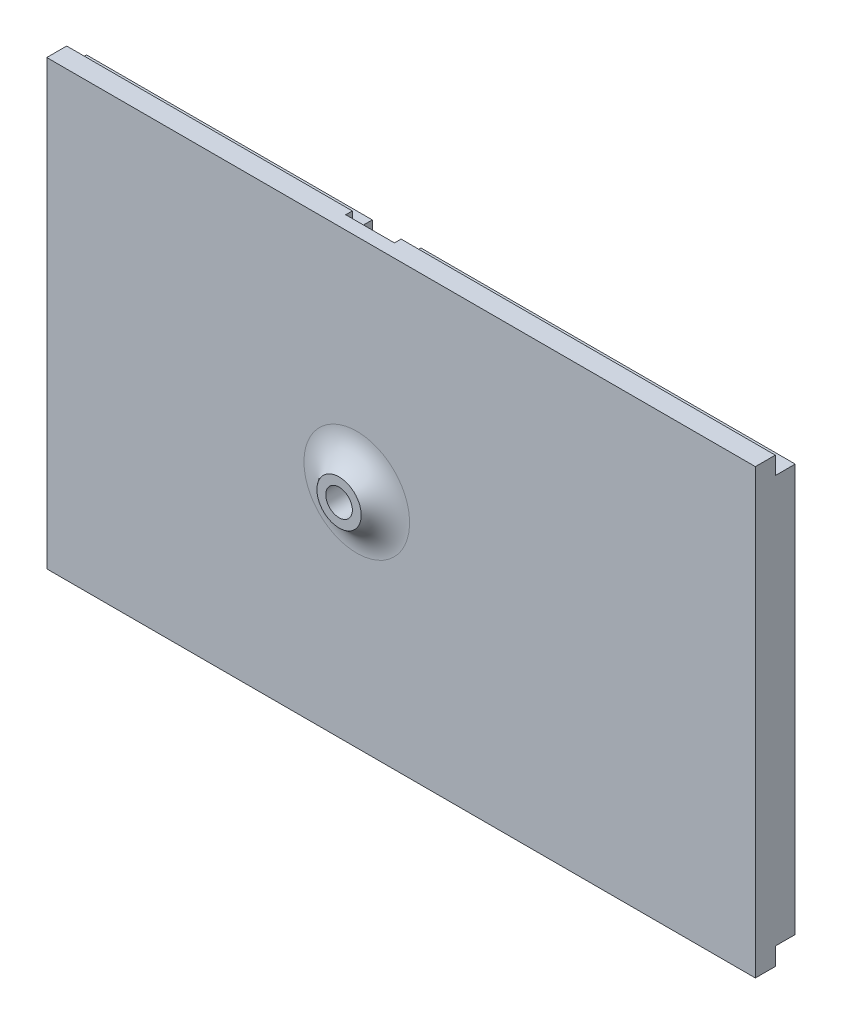
SolidWorks part; units mm, degrees
ref_plane "Front Plane" through (0, 0, 0) normal (1, 0, 0) x (0, 1, 0)
ref_plane "Top Plane" through (0, 0, 0) normal (0, 0, 1) x (0, 1, 0)
ref_plane "Right Plane" through (0, 0, 0) normal (0, 1, 0) x (-1, 0, 0)
sketch "Sketch1" plane through (0, 0, 0) normal (0, 0, 1) x (0, 1, 0)
  line L1 (0, 0) -> (50, 0)
  line L2 (0, 0) -> (0, 80)
  line L3 (0, 80) -> (50, 80)
  line L4 (50, 0) -> (50, 80)
  dimension "D1" = 50
  dimension "D2" = 80
extrude "Boss-Extrude1" add sketch "Sketch1" along normal blind 4.5 contours L3 L4 L1 L2
sketch "Sketch2" plane through (0, 0, 4.5) normal (0, 0, 1) x (1, 0, 0)
  line L0 (-80, 25) -> (0, 25) construction
  line L1 (-80, 0) -> (-80, 50) construction
  line L2 (0, 0) -> (0, 50) construction
  circle A0 centre (-45, 25) radius 0.5
  dimension "D1" = 1
  dimension "D2" = 35
extrude "Cut-Extrude1" cut sketch "Sketch2" against normal through all
sketch "Sketch3" plane through (-80, 0, 0) normal (-1, 0, 0) x (0, -1, 0)
  line L0 (-25, 4.5) -> (-25, 0) construction
  line L1 (0, 4.5) -> (-50, 4.5) construction
  line L2 (0, 0) -> (-50, 0) construction
  line L4 (-50, 2.25) -> (-48, 2.25)
  line L5 (-50, 2.25) -> (-50, 0)
  line L6 (-50, 0) -> (-48, 0)
  line L7 (-48, 2.25) -> (-48, 0)
  line L8 (0, 0) -> (-2, 0)
  line L9 (-2, 2.25) -> (-2, 0)
  line L10 (0, 2.25) -> (-2, 2.25)
  line L11 (0, 2.25) -> (0, 0)
  line L12 (-50, 4.5) -> (-50, 0) construction
  line L13 (0, 4.5) -> (0, 0) construction
  point P11 (0, 0)
  point P18 (0, 0)
  point P21 (0, 0)
  dimension "D1" = 2
extrude "Cut-Extrude2" cut sketch "Sketch3" against normal through all
sketch "Sketch5" plane through (0, 0, 4.5) normal (0, 0, 1) x (1, 0, 0)
  circle A0 centre (-45, 25) radius 2.5
  dimension "D1" = 5
extrude "Boss-Extrude2" add sketch "Sketch5" along normal blind 2
sketch "Sketch6" plane through (0, 0, 6.5) normal (0, 0, 1) x (1, 0, 0)
  circle A0 centre (-45, 25) radius 1.5
  dimension "D1" = 3
extrude "Cut-Extrude3" cut sketch "Sketch6" against normal through all
fillet "Fillet1" radius 4 1 edges at (-47.5, 25, 4.5)
sketch "Sketch8" plane through (0, 0, 0) normal (0, 0, -1) x (1, 0, 0)
  line L0 (0, -50) -> (-80, -50) construction
  line L1 (-47.75, -50) -> (-42.25, -50)
  line L2 (-47.75, -50) -> (-47.75, -20)
  line L3 (-47.75, -20) -> (-42.25, -20)
  line L4 (-42.25, -50) -> (-42.25, -20)
  line L5 (-45, -25) -> (-45, -20) construction
  dimension "D1" = 5.5
  dimension "D2" = 30
extrude "Cut-Extrude4" cut sketch "Sketch8" against normal blind 3
